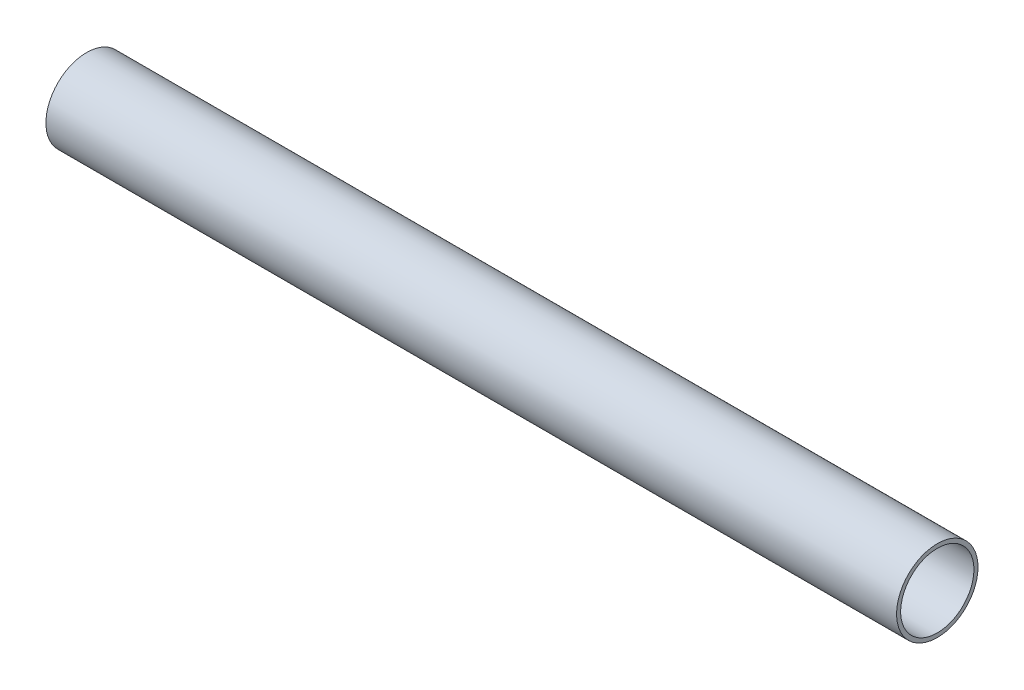
SolidWorks part; units mm, degrees
material "PC High Viscosity"
ref_plane "Front Plane" through (0, 0, 0) normal (0, 0, 1) x (1, 0, 0)
ref_plane "Top Plane" through (0, 0, 0) normal (0, 1, 0) x (1, 0, 0)
ref_plane "Right Plane" through (0, 0, 0) normal (1, 0, 0) x (0, 0, -1)
sketch "Sketch1" plane through (0, 0, 0) normal (1, 0, 0) x (0, 0, -1)
  circle A0 centre (0, 0) radius 15.875
  dimension "D1" = 31.75
extrude "Extrude-Thin1" add sketch "Sketch1" along normal mid plane 331.7875 thin thin type one direction reverse wall 1.5875
sketch "Sketch2" plane through (0, 0, 0) normal (0, 0, 1) x (1, 0, 0)
  line L0 (-165.8938, -15.875) -> (165.8938, -15.875) construction
  line L1 (103.6188, -15.875) -> (124.6188, -15.875)
  line L2 (103.6188, -15.875) -> (103.6188, 15.875)
  line L3 (103.6188, 15.875) -> (124.6188, 15.875)
  line L4 (124.6188, -15.875) -> (124.6188, 15.875)
  line L5 (165.8938, 15.875) -> (-165.8938, 15.875) construction
  line L6 (165.8938, -15.875) -> (165.8938, 15.875) construction
  line L7 (0, 0) -> (0, 11.1276) construction
  line L8 (-124.6188, -15.875) -> (-124.6188, 15.875)
  line L9 (-103.6188, 15.875) -> (-124.6188, 15.875)
  line L10 (-103.6188, -15.875) -> (-103.6188, 15.875)
  line L11 (-103.6188, -15.875) -> (-124.6188, -15.875)
  line L13 (165.8938, -15.875) -> (163.5697, -15.875)
  line L14 (165.8938, -15.875) -> (165.8938, 15.875)
  line L15 (165.8938, 15.875) -> (163.5697, 15.875)
  line L16 (163.5697, -15.875) -> (163.5697, 15.875)
  dimension "D1" = 41.275
  dimension "D2" = 21
  dimension "D3" = 2.3241
equation "\"D2@Sketch2\"=21mm"
